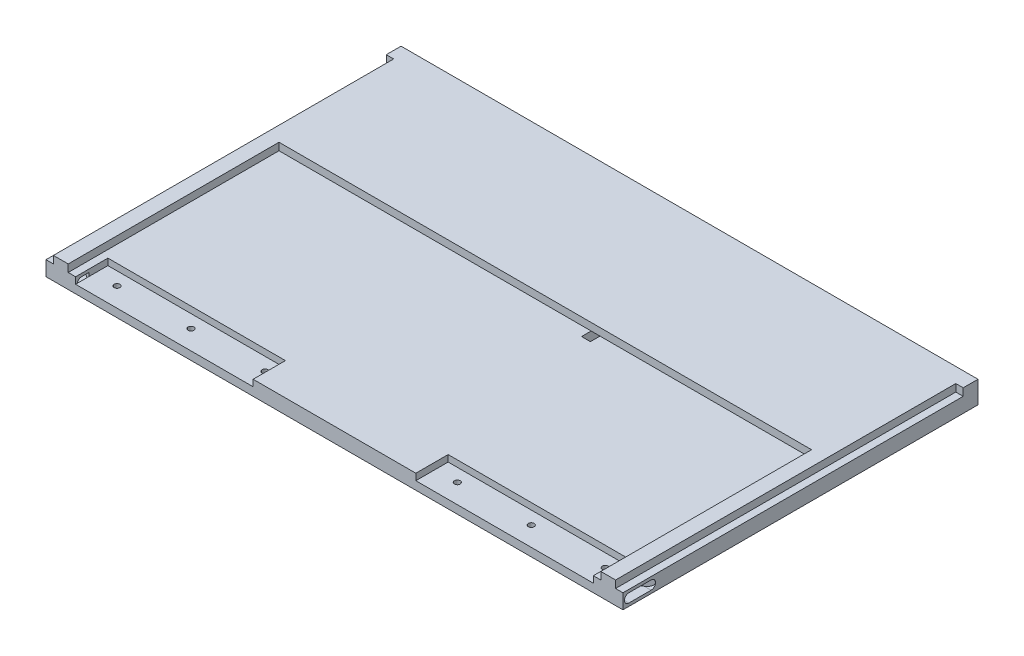
SolidWorks part; units mm, degrees
other "Markup1"
sketch "Sketch12" plane through (250.825, 22.225, 158.75) normal (0.1153, 0.0728, 0.9907) x (0.9687, -0.2289, -0.0959)
material "6061 Alloy"
ref_plane "Front Plane" through (0, 0, 0) normal (0, 0, 1) x (1, 0, 0)
ref_plane "Top Plane" through (0, 0, 0) normal (0, 1, 0) x (1, 0, 0)
ref_plane "Right Plane" through (0, 0, 0) normal (1, 0, 0) x (0, 0, -1)
sketch "Sketch1" plane through (0, 0, 0) normal (0, 1, 0) x (1, 0, 0)
  line L1 (-241.3, 152.4) -> (241.3, 152.4)
  line L2 (-241.3, 152.4) -> (-241.3, -152.4)
  line L3 (-241.3, -152.4) -> (241.3, -152.4)
  line L4 (241.3, 152.4) -> (241.3, -152.4)
  line L5 (-241.3, 152.4) -> (241.3, -152.4) construction
  line L6 (-241.3, -152.4) -> (241.3, 152.4) construction
  circle A0 centre (-203.2, -135.8392) radius 2.5019 construction
  circle A1 centre (-139.7, -135.8392) radius 2.5019 construction
  circle A2 centre (-76.2, -135.8392) radius 2.5019 construction
  circle A3 centre (88.9, -135.8392) radius 2.5019 construction
  circle A4 centre (152.4, -135.8392) radius 2.5019 construction
  circle A5 centre (215.9, -135.8392) radius 2.5019 construction
  circle A6 centre (-203.2, -135.8392) radius 2.5019
  circle A7 centre (-139.7, -135.8392) radius 2.5019
  circle A8 centre (-76.2, -135.8392) radius 2.5019
  circle A9 centre (88.9, -135.8392) radius 2.5019
  circle A10 centre (152.4, -135.8392) radius 2.5019
  circle A11 centre (215.9, -135.8392) radius 2.5019
  point P0 (0, 0)
  dimension "D1" = 482.6
  dimension "D2" = 304.8
extrude "Boss-Extrude1" add sketch "Sketch1" along normal blind 12.7
sketch "Sketch2" plane through (0, 12.7, 0) normal (0, 1, 0) x (1, 0, 0)
  line L0 (-241.3, -152.4) -> (241.3, -152.4) construction
  line L1 (-241.3, 152.4) -> (-228.6, 152.4)
  line L2 (-241.3, 152.4) -> (-241.3, -152.4)
  line L3 (-241.3, -152.4) -> (-228.6, -152.4)
  line L4 (-228.6, 28.575) -> (-228.6, -152.4)
  line L5 (241.3, 152.4) -> (-241.3, 152.4) construction
  line L6 (241.3, 152.4) -> (228.6, 152.4)
  line L7 (241.3, 152.4) -> (241.3, -152.4)
  line L8 (241.3, -152.4) -> (228.6, -152.4)
  line L9 (228.6, 28.575) -> (228.6, -152.4)
  line L10 (-228.6, 152.4) -> (228.6, 152.4)
  line L12 (-228.6, 28.575) -> (228.6, 28.575)
  point P14 (-234.95, -152.4)
  dimension "D1" = 12.7
  dimension "D2" = 180.975
extrude "Boss-Extrude2" add sketch "Sketch2" along normal blind 6.35
sketch "Sketch3" plane through (-241.3, 0, 0) normal (-1, 0, 0) x (0, 0, 1)
  line L0 (152.4, 19.05) -> (152.4, 0) construction
  line L1 (-152.4, 19.05) -> (152.4, 19.05) construction
  circle A0 centre (149.225, 15.875) radius 1.5875
  dimension "D3" = 3.175
  dimension "D1" = 3.175
  dimension "D2" = 3.175
sketch "Sketch4" plane through (0, 0, 152.4) normal (0, 0, 1) x (1, 0, 0)
  line L0 (-241.3, 19.05) -> (-241.3, 0) construction
  line L1 (-241.3, 12.7) -> (-247.65, 12.7)
  line L2 (-241.3, 12.7) -> (-241.3, 0)
  line L3 (-241.3, 0) -> (-247.65, 0)
  line L4 (-247.65, 12.7) -> (-247.65, 0)
  line L5 (-241.3, 0) -> (241.3, 0) construction
  dimension "D1" = 12.7
  dimension "D2" = 6.35
extrude "Boss-Extrude3" add sketch "Sketch4" against normal blind 292.1
sketch "Sketch5" plane through (-241.3, 0, 0) normal (-1, 0, 0) x (0, 0, 1)
  line L0 (-152.4, 0) -> (-139.7, 0) construction
  line L1 (-152.4, 19.05) -> (-139.7, 19.05)
  line L2 (-152.4, 19.05) -> (-152.4, 0)
  line L3 (-152.4, 0) -> (-139.7, 0)
  line L4 (-139.7, 19.05) -> (-139.7, 0)
  line L5 (-139.7, 0) -> (-139.7, 12.7) construction
extrude "Boss-Extrude4" add sketch "Sketch5" along normal up to surface (6.35 mm away) up to face at (-247.65, 6.35, 6.35)
mirror "Mirror1" about plane through (0, 0, 0) normal (1, 0, 0) of "Boss-Extrude4", "Boss-Extrude3"
sketch "Sketch6" plane through (-241.3, 0, 0) normal (-1, 0, 0) x (0, 0, 1)
  line L0 (147.32, 6.35) -> (128.27, 6.35) construction
  line L1 (147.32, 2.54) -> (128.27, 2.54)
  line L2 (147.32, 10.16) -> (128.27, 10.16)
  line L3 (152.4, 19.05) -> (152.4, 12.7) construction
  line L5 (152.4, 12.7) -> (152.4, 0) construction
  arc A0 (147.32, 2.54) -> (147.32, 10.16) centre (147.32, 6.35) ccw
  arc A1 (128.27, 10.16) -> (128.27, 2.54) centre (128.27, 6.35) ccw
  point P2 (137.795, 6.35)
  point P11 (152.4, 6.35)
  dimension "D1" = 19.05
  dimension "D2" = 5.08
  dimension "D3" = 7.62
extrude "Cut-Extrude2" cut sketch "Sketch6" against normal blind 25.4 from surface starting at face at (-247.65, 10.5833, -46.5667)
extrude "Cut-Extrude3" cut sketch "Sketch6<2>" along normal blind 25.4 from surface starting at face at (247.65, 10.5833, -46.5667)
sketch "Sketch6<2>" plane through (-241.3, 0, 0) normal (-1, 0, 0) x (0, 0, 1) same geometry as "Sketch6"
sketch "Sketch11" plane through (0, 0, 0) normal (0, -1, 0) x (1, 0, 0)
  line L0 (-247.65, 124.46) -> (-222.25, 124.46)
  line L1 (-222.25, 124.46) -> (-222.25, 140.97)
  line L2 (-222.25, 140.97) -> (-247.65, 124.46)
  line L3 (-222.25, 128.27) -> (-222.25, 147.32) construction
  dimension "D1" = 10.16
extrude "Boss-Extrude5" add sketch "Sketch11" against normal up to surface (10.16 mm away) from surface up to face at (-234.95, 10.16, 137.795) starting at face at (-234.95, 2.54, 137.795)
mirror "Mirror2" about plane through (0, 0, 0) normal (1, 0, 0) of "Boss-Extrude5"
sketch "Sketch13" plane through (0, 12.7, 0) normal (0, 1, 0) x (1, 0, 0)
  line L0 (228.6, 28.575) -> (228.6, -152.4) construction
  line L1 (222.25, -152.4) -> (69.85, -152.4)
  line L2 (222.25, -152.4) -> (222.25, -124.6632)
  line L3 (222.25, -124.6632) -> (69.85, -124.6632)
  line L4 (69.85, -152.4) -> (69.85, -124.6632)
  line L5 (-228.6, -152.4) -> (228.6, -152.4) construction
  line L6 (0, 0) -> (0, -222.4022) construction
  line L7 (-222.25, -152.4) -> (-222.25, -124.6632)
  line L8 (-222.25, -152.4) -> (-69.85, -152.4)
  line L9 (-69.85, -152.4) -> (-69.85, -124.6632)
  line L10 (-222.25, -124.6632) -> (-69.85, -124.6632)
  dimension "D1" = 27.7368
  dimension "D2" = 6.35
  dimension "D3" = 152.4
extrude "Cut-Extrude4" cut sketch "Sketch13" against normal blind 5.588
sketch "Sketch14" plane through (0, 0, 0) normal (0, -1, 0) x (1, 0, 0)
  line L1 (39.37, -20.32) -> (46.99, -20.32)
  line L2 (39.37, -20.32) -> (39.37, -39.37)
  line L3 (39.37, -39.37) -> (46.99, -39.37)
  line L4 (46.99, -20.32) -> (46.99, -39.37)
  line L7 (247.65, -152.4) -> (-247.65, -152.4) construction
  line L10 (247.65, -152.4) -> (247.65, 152.4) construction
  dimension "D1" = 200.66
  dimension "D2" = 7.62
  dimension "D3" = 19.05
  dimension "D4" = 113.03
extrude "Cut-Extrude5" cut sketch "Sketch14" against normal blind 12.7
